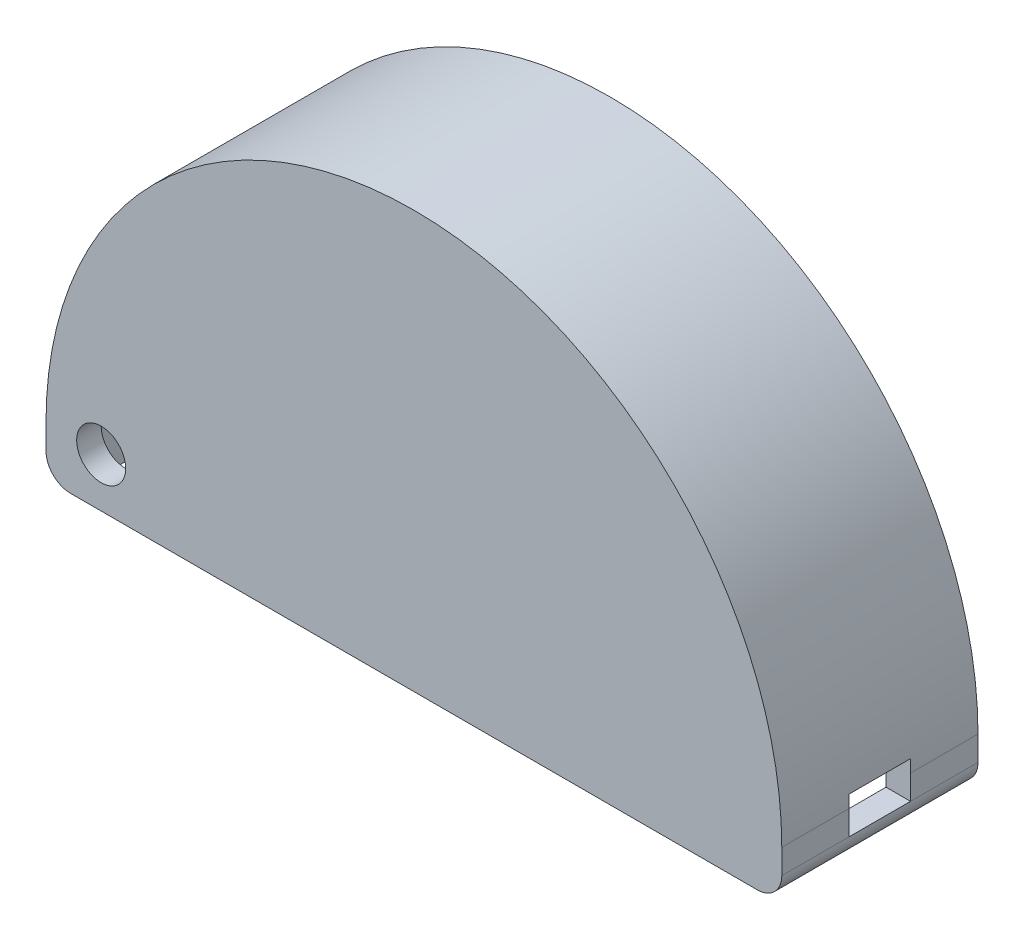
SolidWorks part; units mm, degrees
ref_plane "Front Plane" through (0, 0, 0) normal (0, 0, 1) x (1, 0, 0)
ref_plane "Top Plane" through (0, 0, 0) normal (0, 1, 0) x (1, 0, 0)
ref_plane "Right Plane" through (0, 0, 0) normal (1, 0, 0) x (0, 0, -1)
sketch "Sketch1" plane through (0, 0, 0) normal (0, 0, 1) x (1, 0, 0)
  line L0 (-2.25, -2) -> (27.75, -2)
  line L1 (-2.25, -2) -> (-2.25, 0)
  line L6 (27.75, -2) -> (27.75, 0)
  arc A0 (-2.25, 0) -> (27.75, 0) centre (12.75, 0) cw
  point P4 (0, 0)
  point P5 (12.3187, 0)
  point P6 (0, 0)
  point P9 (27.75, -2)
  point P10 (12.7537, 0)
  point P12 (27.4997, -2)
  point P14 (-1.3673, -0.4691)
  dimension "D1" = 30
  dimension "D2" = 2
  dimension "D5" = 2
  dimension "D6" = 2.25
extrude "Boss-Extrude1" add sketch "Sketch1" along normal blind 4 and the other way blind 4
shell "Shell1" thickness 1 removed face at (12.75, -2, 0)
sketch "Sketch2" plane through (0, 0, 4) normal (0, 0, 1) x (1, 0, 0)
  circle A0 centre (0, 0) radius 1
  dimension "D1" = 2
extrude "Cut-Extrude1" cut sketch "Sketch2" against normal through all both and the other way through all
sketch "Sketch3" plane through (27.75, 0, 0) normal (1, 0, 0) x (0, 0, -1)
  line L0 (4, -2) -> (-4, -2) construction
  line L1 (-1.25, -1) -> (1.25, -1)
  line L2 (-1.25, -1) -> (-1.25, 0.5)
  line L3 (-1.25, 0.5) -> (1.25, 0.5)
  line L4 (1.25, -1) -> (1.25, 0.5)
  point P4 (0, -1)
  dimension "D1" = 2.5
  dimension "D2" = 1.5
  dimension "D3" = 1
extrude "Cut-Extrude2" cut sketch "Sketch3" against normal up to surface (1.0358 mm away) up to face at (12.75, 7, 0)
fillet "Fillet2" radius 1 2 edges at (27.75, -2, 0) (-2.25, -2, 0)
